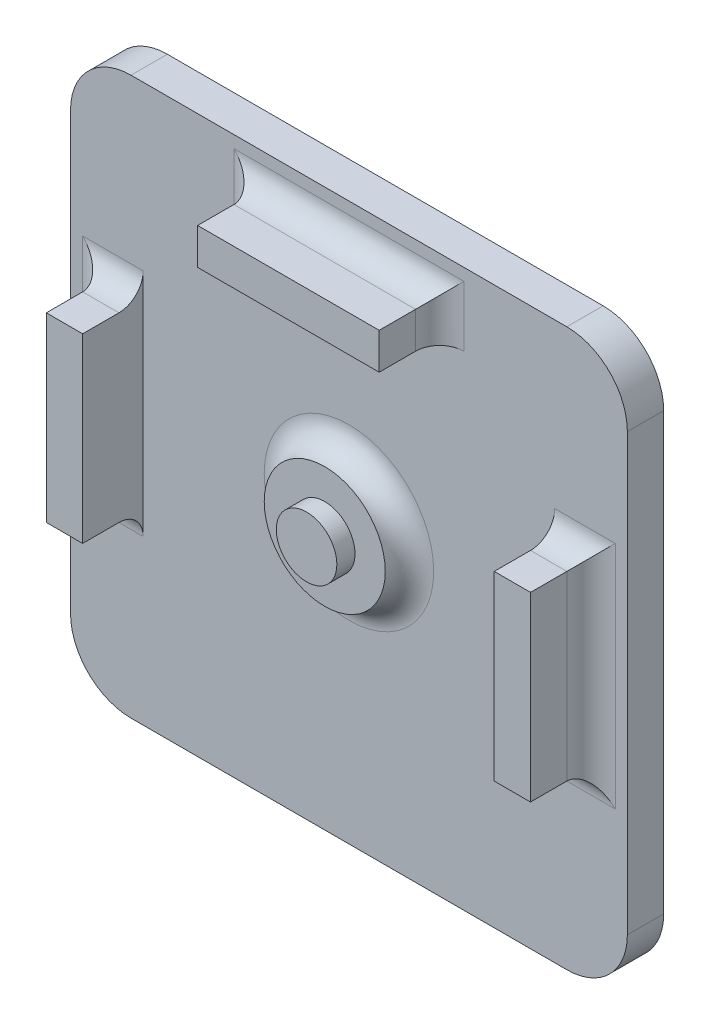
SolidWorks part; units mm, degrees
ref_plane "正面" through (0, 0, 0) normal (0, 0, 1) x (1, 0, 0)
ref_plane "平面" through (0, 0, 0) normal (0, 1, 0) x (1, 0, 0)
ref_plane "右側面" through (0, 0, 0) normal (1, 0, 0) x (0, 0, -1)
sketch "ｽｹｯﾁ1" plane through (0, 0, 0) normal (0, 0, 1) x (1, 0, 0)
  line L1 (0, 0) -> (46, 0)
  line L2 (0, 0) -> (0, 46)
  line L3 (0, 46) -> (46, 46)
  line L4 (46, 0) -> (46, 46)
  dimension "D1" = 46
  dimension "D2" = 46
extrude "ﾎﾞｽ - 押し出し1" add sketch "ｽｹｯﾁ1" along normal blind 3
sketch "ｽｹｯﾁ3" plane through (0, 0, 3) normal (0, 0, 1) x (1, 0, 0)
  circle A0 centre (23, 23) radius 5
  dimension "D1" = 10
extrude "ﾎﾞｽ - 押し出し2" add sketch "ｽｹｯﾁ3" along normal blind 2
sketch "ｽｹｯﾁ4" plane through (0, 0, 5) normal (0, 0, 1) x (1, 0, 0)
  circle A0 centre (23, 23) radius 2.5
  dimension "D1" = 5
extrude "ﾎﾞｽ - 押し出し3" add sketch "ｽｹｯﾁ4" along normal blind 1.5
fillet "ﾌｨﾚｯﾄ1" radius 5 4 edges at (0, 0, 1.5) (46, 0, 1.5) (46, 46, 1.5) (0, 46, 1.5)
fillet "ﾌｨﾚｯﾄ2" radius 2 1 edges at (28, 23, 3)
sketch "ｽｹｯﾁ5" plane through (0, 0, 3) normal (0, 0, 1) x (1, 0, 0)
  line L1 (6, 40) -> (40, 40) construction
  line L2 (6, 40) -> (6, 6) construction
  line L3 (6, 6) -> (40, 6) construction
  line L4 (40, 40) -> (40, 6) construction
  line L5 (6, 40) -> (40, 6) construction
  line L6 (6, 6) -> (40, 40) construction
  line L7 (6, 30.5) -> (3, 30.5)
  line L8 (6, 30.5) -> (6, 15.5)
  line L9 (6, 15.5) -> (3, 15.5)
  line L10 (3, 30.5) -> (3, 15.5)
  line L11 (6, 30.5) -> (3, 15.5) construction
  line L12 (6, 15.5) -> (3, 30.5) construction
  line L13 (15.5, 40) -> (30.5, 40)
  line L14 (15.5, 40) -> (15.5, 43)
  line L15 (15.5, 43) -> (30.5, 43)
  line L16 (30.5, 40) -> (30.5, 43)
  line L17 (15.5, 40) -> (30.5, 43) construction
  line L18 (15.5, 43) -> (30.5, 40) construction
  line L19 (40, 30.5) -> (43, 30.5)
  line L20 (40, 30.5) -> (40, 15.5)
  line L21 (40, 15.5) -> (43, 15.5)
  line L22 (43, 30.5) -> (43, 15.5)
  line L23 (40, 30.5) -> (43, 15.5) construction
  line L24 (40, 15.5) -> (43, 30.5) construction
  circle A0 centre (23, 23) radius 2.5 construction
  point P4 (23, 23)
  point P11 (4.5, 23)
  point P16 (23, 41.5)
  point P21 (41.5, 23)
  dimension "D1" = 34
  dimension "D2" = 34
  dimension "D3" = 15
  dimension "D4" = 15
  dimension "D5" = 15
  dimension "D6" = 3
  dimension "D7" = 3
  dimension "D8" = 3
extrude "ﾎﾞｽ - 押し出し4" add sketch "ｽｹｯﾁ5" along normal blind 5
fillet "ﾌｨﾚｯﾄ3" radius 2 9 edges at (4.5, 30.5, 3) (3, 23, 3) (4.5, 15.5, 3) (41.5, 15.5, 3) (41.5, 30.5, 3) (43, 23, 3) (30.5, 41.5, 3) (23, 43, 3) (15.5, 41.5, 3)
